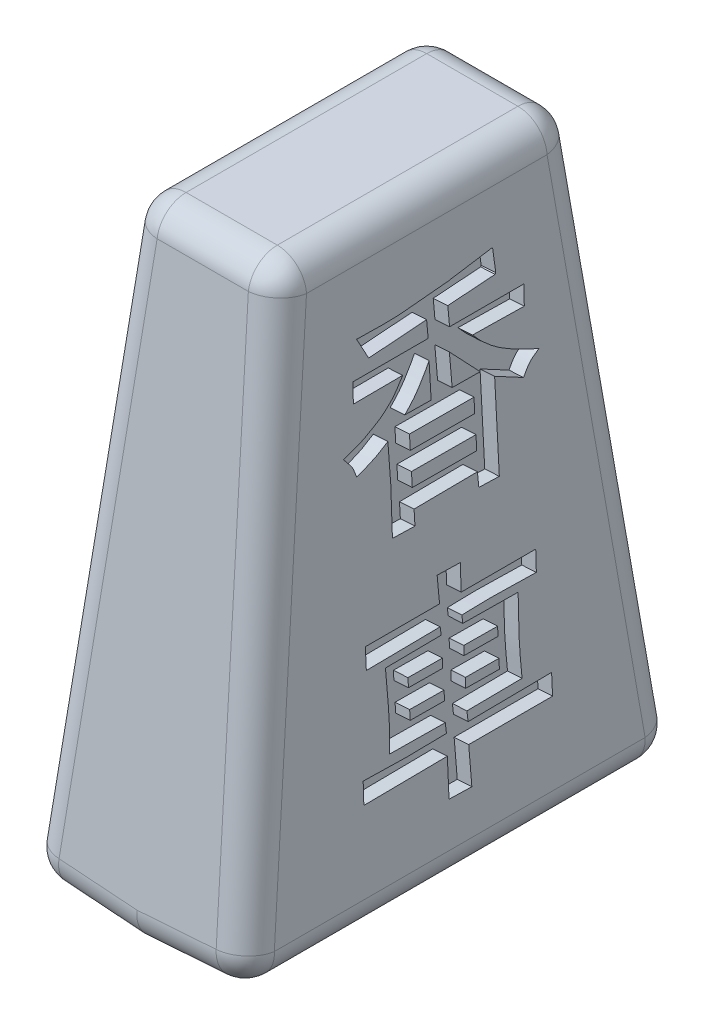
SolidWorks part; units mm, degrees
ref_plane "Płaszczyzna przednia" through (0, 0, 0) normal (0, 0, 1) x (1, 0, 0)
ref_plane "Płaszczyzna górna" through (0, 0, 0) normal (0, 1, 0) x (1, 0, 0)
ref_plane "Płaszczyzna prawa" through (0, 0, 0) normal (1, 0, 0) x (0, 0, -1)
sketch "Szkic1" plane through (0, 0, 0) normal (0, 0, 1) x (1, 0, 0)
  line L0 (0, 0) -> (0, 40)
  line L1 (3.1225, 40) -> (-3.1225, 40)
  line L2 (-5.1185, 38.1262) -> (-7.3738, 2.4704)
  line L3 (-5.504, 0.3481) -> (0, 0)
  line L4 (5.504, 0.3481) -> (0, 0)
  line L5 (5.1185, 38.1262) -> (7.3738, 2.4704)
  arc A0 (-3.1225, 40) -> (-5.1185, 38.1262) centre (-3.1225, 38) ccw
  arc A1 (-7.3738, 2.4704) -> (-5.504, 0.3481) centre (-5.3777, 2.3441) ccw
  arc A2 (7.3738, 2.4704) -> (5.504, 0.3481) centre (5.3777, 2.3441) cw
  arc A3 (3.1225, 40) -> (5.1185, 38.1262) centre (3.1225, 38) cw
  point P7 (-5, 40)
  point P10 (-7.5, 0.4744)
  point P17 (7.5, 0.4744)
  point P18 (5, 40)
  dimension "D5" = 2
  dimension "D1" = 40
  dimension "D2" = 90
  dimension "D3" = 5
  dimension "D4" = 7.5
extrude "Dodanie-wyciągnięcie1" add sketch "Szkic1" along normal blind 30 contours L2 A1 L3 L0 L1 A0 | A3 L1 L0 L4 A2 L5 region at (-3.1441, 18.7866, 0) region at (3.1441, 18.7866, 0)
ref_plane "Płaszczyzna1" through (5.1225, 0, 0) normal (1, 0, 0) x (0, 0, -1)
ref_plane "Płaszczyzna2" through (15.1225, 0, 0) normal (1, 0, 0) x (0, 0, -1)
sketch "Szkic7" plane through (15.1225, 0, 0) normal (1, 0, 0) x (0, 0, -1)
  line L0 (-25, 40) -> (-5, 40)
  line L1 (-30, 40) -> (0, 40) construction
  line L2 (-5, 40) -> (0, 0)
  line L3 (0, 0) -> (-30, 0)
  line L4 (-30, 0) -> (0, 0) construction
  line L5 (-15, 0) -> (-15, 40)
  line L6 (-25, 40) -> (-30, 0)
  line L8 (0, 0) -> (-30, 0)
  line L9 (0, 0) -> (0, 40)
  line L10 (0, 40) -> (-30, 40)
  line L11 (-30, 0) -> (-30, 40)
  dimension "D1" = 10
  dimension "D2" = 15
  dimension "D3" = 40
extrude "Wytnij-wyciągnięcie11" cut sketch "Szkic7" against normal through all and the other way through all contours L11 L6 L10 | L9 L10 L2 region at (15.1225, 26.6667, 28.3333) region at (15.1225, 26.6667, 1.6667)
fillet "Zaokrąglenie2" radius 2 18 edges at (0, 40, 5) (-4.4914, 39.4582, 4.9323) (-6.2461, 20.2983, 2.5373) (-6.8784, 1.022, 0.1278) (-2.752, 0.1741, 0.0218) (2.752, 0.1741, 0.0218) (6.8784, 1.022, 0.1278) (6.2461, 20.2983, 2.5373) (4.4914, 39.4582, 4.9323) (4.4914, 39.4582, 25.0677) (6.2461, 20.2983, 27.4627) (6.8784, 1.022, 29.8722) (2.752, 0.1741, 29.9782) (-2.752, 0.1741, 29.9782) (-6.8784, 1.022, 29.8722) (-6.2461, 20.2983, 27.4627) (-4.4914, 39.4582, 25.0677) (0, 40, 25)
sketch "Szkic8" plane through (7.5, 0.4744, 0) normal (0.998, 0.0631, 0) x (0, 0, -1)
  line L0 (341.3333, 1024) -> (1706.6667, 1024) construction
  line L1 (-10.7093, 34.2759) -> (-10.5893, 32.7959)
  line L2 (-10.5893, 32.7959) -> (-10.6293, 32.7159)
  line L3 (-10.6293, 32.7159) -> (-13.8893, 32.4959)
  line L4 (-13.8893, 32.4959) -> (-13.8493, 31.2559)
  line L5 (-13.8493, 31.2559) -> (-8.7693, 31.2559)
  line L6 (-8.7693, 31.2559) -> (-8.8093, 29.9959)
  line L7 (-8.8093, 29.9959) -> (-12.3493, 30.0559)
  line L8 (-9.1093, 26.0359) -> (-11.0293, 27.0359)
  line L9 (-11.0293, 27.0359) -> (-11.0693, 21.2959)
  line L10 (-11.0693, 21.2959) -> (-12.4693, 21.3359)
  line L11 (-12.4693, 21.3359) -> (-12.5093, 22.2559)
  line L12 (-12.5093, 22.2559) -> (-16.8493, 22.2159)
  line L13 (-16.8493, 22.2159) -> (-16.8493, 21.2359)
  line L14 (-16.8493, 21.2359) -> (-18.3893, 21.2759)
  line L15 (-17.1293, 30.0559) -> (-20.5093, 30.0359)
  line L16 (-20.5093, 30.0359) -> (-20.4693, 31.2959)
  line L17 (-20.4693, 31.2959) -> (-15.3093, 31.2959)
  line L18 (-15.3093, 31.2959) -> (-15.3493, 32.3959)
  line L19 (-15.3493, 32.3959) -> (-19.3293, 32.1159)
  line L20 (-19.3293, 32.1159) -> (-20.0693, 33.5559)
  line L21 (-15.3293, 30.0359) -> (-15.3293, 27.7559)
  line L22 (-15.3293, 27.7559) -> (-17.1293, 27.7759)
  line L23 (-13.9493, 29.8559) -> (-11.9693, 27.7559)
  line L24 (-11.9693, 27.7559) -> (-13.8893, 27.7759)
  line L25 (-13.8893, 27.7759) -> (-13.9493, 29.8559)
  line L26 (-16.8893, 26.5559) -> (-12.4693, 26.5359)
  line L27 (-12.4693, 26.5359) -> (-12.4893, 25.5959)
  line L28 (-12.4893, 25.5959) -> (-16.8893, 25.6159)
  line L29 (-16.8893, 25.6159) -> (-16.8893, 26.5559)
  line L30 (-16.8893, 24.3959) -> (-12.4693, 24.3759)
  line L31 (-12.4693, 24.3759) -> (-12.4893, 23.4559)
  line L32 (-12.4893, 23.4559) -> (-16.8893, 23.4759)
  line L33 (-16.8893, 23.4759) -> (-16.8893, 24.3959)
  line L34 (-15.5493, 17.7759) -> (-13.9693, 17.7359)
  line L35 (-13.9693, 17.7359) -> (-14.0093, 16.0559)
  line L36 (-14.0093, 16.0559) -> (-8.9093, 16.0559)
  line L37 (-8.9093, 16.0559) -> (-8.9493, 14.7359)
  line L38 (-14.0493, 14.7559) -> (-14.0093, 14.2559)
  line L39 (-14.0093, 14.2559) -> (-10.2293, 14.2159)
  line L40 (-10.2693, 9.2759) -> (-14.0493, 9.2359)
  line L41 (-14.0493, 9.2359) -> (-14.0093, 8.5959)
  line L42 (-14.0093, 8.5959) -> (-8.2893, 8.6559)
  line L43 (-8.2893, 8.6559) -> (-8.3093, 7.2959)
  line L44 (-8.3093, 7.2959) -> (-14.0493, 7.2959)
  line L45 (-14.0493, 7.2959) -> (-13.9893, 4.8359)
  line L46 (-13.9893, 4.8359) -> (-15.5493, 4.8759)
  line L47 (-15.5493, 4.8759) -> (-15.5093, 7.3359)
  line L48 (-15.5093, 7.3359) -> (-21.2293, 7.2759)
  line L49 (-21.2293, 7.2759) -> (-21.1893, 8.6559)
  line L50 (-15.4893, 8.6359) -> (-15.5293, 9.2759)
  line L51 (-15.5293, 9.2759) -> (-19.3293, 9.3159)
  line L52 (-19.3093, 14.2559) -> (-15.4893, 14.2959)
  line L53 (-15.4893, 14.2959) -> (-15.5293, 14.7959)
  line L54 (-15.5293, 14.7959) -> (-20.5893, 14.7359)
  line L55 (-20.5893, 14.7359) -> (-20.5693, 16.0959)
  line L56 (-20.5693, 16.0959) -> (-15.4893, 16.0959)
  line L57 (-15.4893, 16.0959) -> (-15.5493, 17.7759)
  line L58 (-17.8493, 12.9959) -> (-15.4893, 12.9759)
  line L59 (-15.4893, 12.9759) -> (-15.5093, 12.3959)
  line L60 (-15.5093, 12.3959) -> (-17.8493, 12.4159)
  line L61 (-17.8493, 12.4159) -> (-17.8493, 12.9959)
  line L62 (-14.0293, 12.9959) -> (-11.7093, 12.9759)
  line L63 (-11.7093, 12.9759) -> (-11.7293, 12.3959)
  line L64 (-11.7293, 12.3959) -> (-14.0493, 12.4159)
  line L65 (-14.0493, 12.4159) -> (-14.0293, 12.9959)
  line L66 (-17.8493, 11.1559) -> (-15.4893, 11.1359)
  line L67 (-15.4893, 11.1359) -> (-15.5093, 10.5159)
  line L68 (-15.5093, 10.5159) -> (-17.8493, 10.5359)
  line L69 (-17.8493, 10.5359) -> (-17.8493, 11.1559)
  line L70 (-14.0293, 11.1559) -> (-11.7293, 11.1359)
  line L71 (-11.7293, 11.1359) -> (-11.7493, 10.5159)
  line L72 (-11.7493, 10.5159) -> (-14.0493, 10.5359)
  line L73 (-14.0493, 10.5359) -> (-14.0293, 11.1559)
  spline S0 degree 3 poles (-20.0693, 33.5559) (-18.9893, 33.5559) (-17.9045, 33.4745) (-16.8293, 33.5759) (-15.7831, 33.6746) (-14.7355, 33.7572) (-13.6893, 33.8559) (-13.6744, 33.8573) (-13.664, 33.8737) (-13.6493, 33.8759) (-12.7766, 34.0071) (-11.9019, 34.1247) (-11.0293, 34.2559) (-10.8965, 34.2759) (-10.8416, 34.3288) (-10.7093, 34.2759) knots 0 0 0 0 1 1 1 2 2 2 3 3 3 4 4 4 5 5 5 5
  spline S1 degree 3 poles (-12.3493, 30.0559) (-12.1559, 29.8426) (-11.9817, 29.6102) (-11.7693, 29.4159) (-11.4335, 29.1088) (-11.0864, 28.8105) (-10.7093, 28.5559) (-10.2837, 28.2686) (-9.8259, 28.0309) (-9.3693, 27.7959) (-8.9184, 27.5639) (-8.4493, 27.3693) (-7.9893, 27.1559) knots 0 0 0 0 1 1 1 2 2 2 3 3 3 4 4 4 4
  spline S2 degree 3 poles (-7.9893, 27.1559) (-8.1693, 27.0359) (-8.3663, 26.9381) (-8.5293, 26.7959) (-8.7694, 26.5864) (-8.9453, 26.3092) (-9.1093, 26.0359) knots 0 0 0 0 1 1 1 2 2 2 2
  spline S3 degree 3 poles (-18.3893, 21.2759) (-18.3626, 22.2959) (-18.3166, 23.3156) (-18.3093, 24.3359) (-18.3033, 25.1693) (-18.3359, 26.0026) (-18.3493, 26.8359) knots 0 0 0 0 1 1 1 2 2 2 2
  spline S4 degree 3 poles (-18.3493, 26.8359) (-18.6693, 26.6626) (-18.9768, 26.464) (-19.3093, 26.3159) (-19.712, 26.1365) (-20.1359, 26.0093) (-20.5493, 25.8559) knots 0 0 0 0 1 1 1 2 2 2 2
  spline S5 degree 3 poles (-20.5493, 25.8559) (-20.6293, 26.0693) (-20.6762, 26.2981) (-20.7893, 26.4959) (-20.9474, 26.7726) (-21.184, 26.9966) (-21.3693, 27.2559) knots 0 0 0 0 1 1 1 2 2 2 2
  spline S6 degree 3 poles (-21.3693, 27.2559) (-20.8341, 27.444) (-20.2679, 27.5655) (-19.7693, 27.8359) (-19.4152, 28.0279) (-19.0433, 28.1909) (-18.7093, 28.4159) (-18.407, 28.6196) (-18.1222, 28.8534) (-17.8693, 29.1159) (-17.5926, 29.4031) (-17.3759, 29.7426) (-17.1293, 30.0559) knots 0 0 0 0 1 1 1 2 2 2 3 3 3 4 4 4 4
  spline S7 degree 3 poles (-17.1293, 27.7759) (-16.9515, 27.9537) (-16.7645, 28.1131) (-16.5893, 28.2959) (-16.235, 28.6655) (-15.9323, 29.0914) (-15.6493, 29.5159) (-15.6488, 29.5167) (-15.3293, 29.989) (-15.3293, 30.0359) knots 0 0 0 0 1 1 1 2 2 2 3 3 3 3
  spline S8 degree 3 poles (-8.9493, 14.7359) (-9.9759, 14.7559) (-11.0024, 14.7919) (-12.0293, 14.7959) (-12.7027, 14.7986) (-13.3759, 14.7693) (-14.0493, 14.7559) knots 0 0 0 0 1 1 1 2 2 2 2
  spline S9 degree 3 poles (-10.2293, 14.2159) (-10.2626, 13.2626) (-10.3216, 12.3098) (-10.3293, 11.3559) (-10.3349, 10.6623) (-10.2893, 9.9693) (-10.2693, 9.2759) knots 0 0 0 0 1 1 1 2 2 2 2
  spline S10 degree 3 poles (-21.1893, 8.6559) (-20.2026, 8.6359) (-19.2161, 8.5994) (-18.2293, 8.5959) (-17.3159, 8.5927) (-16.4026, 8.6226) (-15.4893, 8.6359) knots 0 0 0 0 1 1 1 2 2 2 2
  spline S11 degree 3 poles (-19.3293, 9.3159) (-19.2955, 10.2223) (-19.2172, 11.1294) (-19.2493, 12.0359) (-19.2755, 12.7757) (-19.2893, 13.5159) (-19.3093, 14.2559) knots 0 0 0 0 1 1 1 2 2 2 2
extrude "Wytnij-wyciągnięcie12" cut sketch "Szkic8" against normal blind 1 contours S6 S5 S4 S3 L14 L13 L12 L11 L10 L9 L8 S2 S1 L7 L6 L5 L4 L3 L2 L1 S0 L20 L19 L18 L17 L16 L15 L24 L25 L23 L28 L29 L26 L27 L32 L33 L30 L31 L22 S7 L21 | S11 L51 L50 S10 L49 L48 L47 L46 L45 L44 L43 L42 L41 L40 S9 L39 L38 S8 L37 L36 L35 L34 L57 L56 L55 L54 L53 L52 L72 L73 L70 L71 L68 L69 L66 L67 L64 L65 L62 L63 L60 L61 L58 L59 region at (5.7304, 28.4522, 14.8179) region at (6.7711, 11.9992, 14.7767)
sketch "Szkic9" plane through (-7.5, 0.4744, 0) normal (-0.998, 0.0631, 0) x (0, 0, 1)
  line L0 (341.3333, 1024) -> (1706.6667, 1024) construction
  line L14 (23.9972, 21.986) -> (16.4292, 21.778)
  line L15 (16.4292, 21.778) -> (16.4932, 25.202)
  line L16 (13.9972, 25.186) -> (14.0772, 21.778)
  line L17 (14.0772, 21.778) -> (6.1732, 22.018)
  line L19 (5.8692, 19.89) -> (12.4132, 20.018)
  line L22 (13.9812, 13.506) -> (9.1172, 13.474)
  line L23 (9.1172, 13.474) -> (9.0692, 4.354)
  line L24 (11.5652, 4.37) -> (11.5012, 6.114)
  line L25 (11.5012, 6.114) -> (19.0692, 6.082)
  line L26 (19.0692, 6.082) -> (19.1012, 4.434)
  line L27 (19.1012, 4.434) -> (21.4212, 4.466)
  line L28 (21.4212, 4.466) -> (21.3892, 13.506)
  line L29 (21.3892, 13.506) -> (16.4932, 13.538)
  line L30 (16.4932, 13.538) -> (16.4292, 17.698)
  line L34 (11.4692, 11.506) -> (19.0692, 11.49)
  line L35 (19.0692, 11.49) -> (19.0532, 8.13)
  line L36 (19.0532, 8.13) -> (11.4692, 8.146)
  line L37 (11.4692, 8.146) -> (11.4692, 11.506)
  line L38 (4.9892, 13.394) -> (5.1492, 14.658)
  line L39 (5.8692, 19.89) -> (6.1732, 22.018)
  line L40 (23.9972, 21.986) -> (24.3172, 19.874)
  line L41 (25.0372, 14.69) -> (24.9412, 15.266)
  spline S0 degree 3 poles (16.4932, 25.202) (16.0452, 25.1807) (15.5977, 25.1409) (15.1492, 25.138) (14.7648, 25.1356) (14.3812, 25.17) (13.9972, 25.186) knots 0 0 0 0 1 1 1 2 2 2 2
  spline S1 degree 3 poles (12.4132, 20.018) (10.8988, 18.1251) (9.1508, 16.705) (7.0372, 15.586) (6.4182, 15.2583) (5.7765, 14.9717) (5.1492, 14.658) knots 0 0 0 0 1 1 1 2 2 2 2
  spline S2 degree 3 poles (17.6292, 19.954) (19.7572, 19.9433) (21.9065, 20.207) (24.0132, 19.906) (24.114, 19.8916) (24.2158, 19.8847) (24.3172, 19.874) knots 0 0 0 0 1 1 1 2 2 2 2
  spline S3 degree 3 poles (24.9412, 15.266) (24.2792, 15.4668) (23.5968, 15.6107) (22.9572, 15.874) (22.5148, 16.0562) (22.0603, 16.2108) (21.6292, 16.418) (21.2374, 16.6063) (20.8573, 16.8207) (20.4932, 17.058) (20.1357, 17.291) (19.7899, 17.5447) (19.4692, 17.826) (18.7642, 18.4443) (18.2014, 19.2111) (17.6292, 19.954) knots 0 0 0 0 1 1 1 2 2 2 3 3 3 4 4 4 5 5 5 5
  spline S4 degree 3 poles (14.0772, 18.21) (14.061, 16.7433) (14.2206, 15.2621) (14.0132, 13.81) (13.9987, 13.7092) (13.9918, 13.6074) (13.9812, 13.506) knots 0 0 0 0 1 1 1 2 2 2 2
  spline S5 degree 3 poles (9.0692, 4.354) (9.5916, 4.3758) (10.1149, 4.4281) (10.6372, 4.402) (10.9463, 4.3866) (11.2558, 4.3807) (11.5652, 4.37) knots 0 0 0 0 1 1 1 2 2 2 2
  spline S6 degree 3 poles (16.4292, 17.698) (16.6958, 17.426) (16.9443, 17.1349) (17.2292, 16.882) (18.1674, 16.0492) (19.1287, 15.2224) (20.2052, 14.578) (20.5941, 14.3452) (20.9944, 14.1297) (21.4052, 13.938) (21.8755, 13.7186) (22.358, 13.5249) (22.8452, 13.346) (23.2015, 13.2152) (23.5705, 13.122) (23.9332, 13.01) knots 0 0 0 0 1 1 1 2 2 2 3 3 3 4 4 4 5 5 5 5
  spline S7 degree 3 poles (23.9332, 13.01) (24.0132, 13.2234) (24.0653, 13.4493) (24.1732, 13.65) (24.2964, 13.8794) (24.4548, 14.0897) (24.6212, 14.29) (24.7441, 14.438) (24.8985, 14.5567) (25.0372, 14.69) knots 0 0 0 0 1 1 1 2 2 2 3 3 3 3
  spline S8 degree 3 poles (4.9892, 13.394) (5.1385, 13.1647) (5.3033, 12.9447) (5.4372, 12.706) (5.5492, 12.5062) (5.6292, 12.29) (5.7252, 12.082) knots 0 0 0 0 1 1 1 2 2 2 2
  spline S9 degree 3 poles (5.7252, 12.082) (6.3801, 12.4095) (7.0496, 12.7087) (7.6932, 13.058) (8.1811, 13.3229) (8.6559, 13.613) (9.1172, 13.922) (9.7234, 14.3282) (10.3156, 14.756) (10.8932, 15.202) (11.3936, 15.5885) (11.8845, 15.9891) (12.3492, 16.418) (12.9589, 16.9809) (13.5397, 17.5778) (14.0772, 18.21) knots 0 0 0 0 1 1 1 2 2 2 3 3 3 4 4 4 5 5 5 5
extrude "Wytnij-wyciągnięcie13" cut sketch "Szkic9" against normal blind 1 contours S8 S9 S4 L22 L23 S5 L24 L25 L26 L27 L28 L29 L30 S6 S7 L41 S3 S2 L40 L14 L15 S0 L16 L17 L39 L19 S1 L38 L36 L37 L34 L35 region at (-6.575, 15.0987, 14.95)
